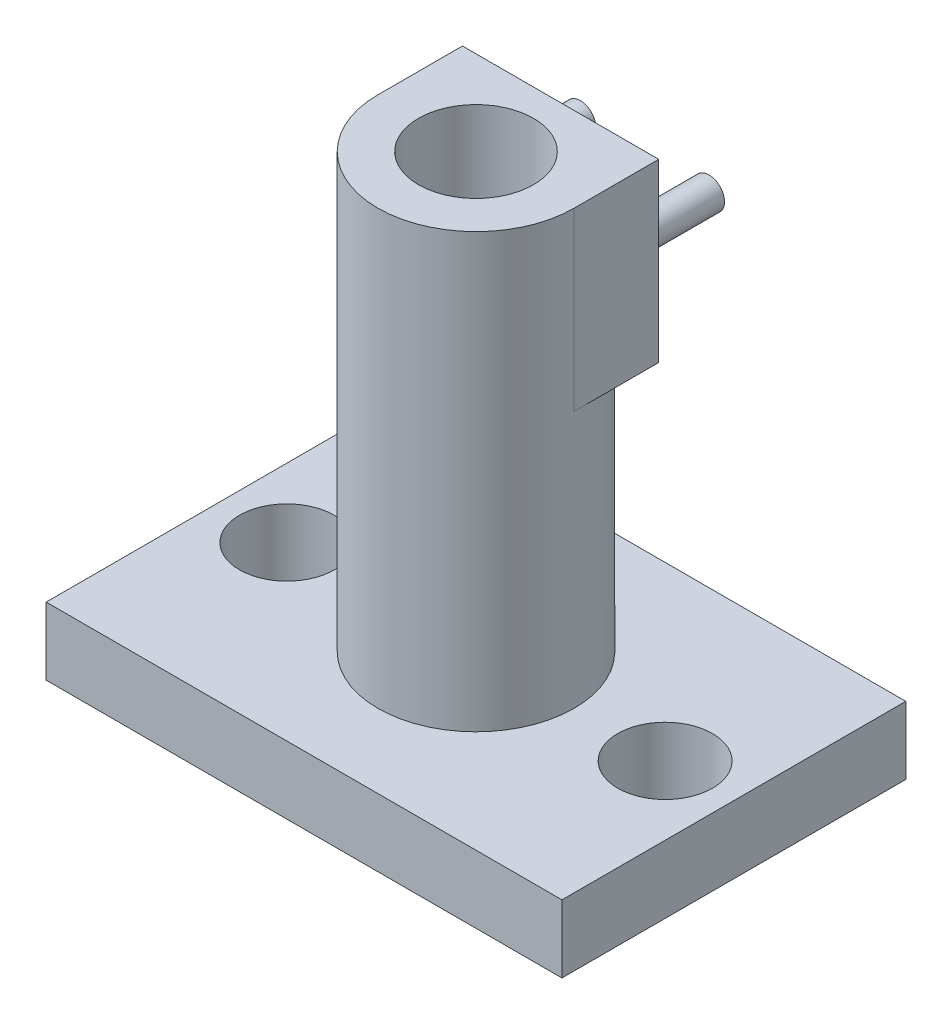
SolidWorks part; units mm, degrees
ref_plane "前视" through (0, 0, 0) normal (0, 0, 1) x (1, 0, 0)
ref_plane "上视" through (0, 0, 0) normal (0, 1, 0) x (1, 0, 0)
ref_plane "右视" through (0, 0, 0) normal (1, 0, 0) x (0, 0, -1)
sketch "Sketch1" plane through (0, 0, 0) normal (0, 1, 0) x (1, 0, 0)
  line L1 (-25.8417, 12.7) -> (12.2583, 12.7)
  line L2 (-25.8417, 12.7) -> (-25.8417, -12.7)
  line L3 (-25.8417, -12.7) -> (12.2583, -12.7)
  line L4 (12.2583, 12.7) -> (12.2583, -12.7)
  dimension "D1" = 25.4
  dimension "D2" = 38.1
extrude "Boss-Extrude1" add sketch "Sketch1" along normal blind 5
ref_point "Point1"
sketch "Sketch3" plane through (0, 5, 0) normal (0, 1, 0) x (1, 0, 0)
  circle A0 centre (-6.7917, 0) radius 7.25
  circle A1 centre (-6.7917, 0) radius 4.25
  dimension "D1" = 8.5
  dimension "D2" = 3
extrude "Boss-Extrude2" add sketch "Sketch3" along normal blind 32
ref_axis "Axis1" through (12.2583, 5, 0) along (-1, 0, 0)
sketch "Sketch4" plane through (0, 5, 0) normal (0, 1, 0) x (1, 0, 0)
  line L0 (12.2583, -12.7) -> (12.2583, 12.7) construction
  line L1 (-25.8417, 12.7) -> (-25.8417, -12.7) construction
  circle A0 centre (7.1783, 0) radius 3.5
  circle A1 centre (-20.7617, 0) radius 3.5
  point P0 (7.1783, 0)
  point P1 (12.2583, 0)
  point P4 (-20.7617, 0)
  dimension "D3" = 7
  dimension "D4" = 7
  dimension "D1" = 5.08
  dimension "D2" = 5.08
extrude "Cut-Extrude1" cut sketch "Sketch4" against normal through all
sketch "Sketch6" plane through (0, 37, 0) normal (0, 1, 0) x (1, 0, 0)
  line L0 (-3.1175, 6.25) -> (-10.466, 6.25)
  line L1 (12.2583, 0) -> (-25.8417, 0) construction
  circle A2 centre (-6.7917, 0) radius 7.25 construction
  arc A3 (-3.1175, 6.25) -> (-10.466, 6.25) centre (-6.7917, 0) ccw
  dimension "D1" = 6.25
extrude "Cut-Extrude2" cut sketch "Sketch6" against normal blind 18
sketch "Sketch8" plane through (0, 37, 0) normal (0, 1, 0) x (1, 0, 0)
  line L0 (-10.466, 6.25) -> (-3.1175, 6.25) construction
  line L1 (-14.0417, 6.25) -> (-10.466, 6.25)
  line L2 (0.4583, 0) -> (0.4583, 6.25)
  line L3 (-14.0417, 0) -> (-14.0417, 6.25)
  line L4 (-3.1175, 6.25) -> (0.4583, 6.25)
  arc A0 (-10.466, 6.25) -> (-3.1175, 6.25) centre (-6.7917, 0) ccw construction
  arc A1 (-10.466, 6.25) -> (-14.0417, 0) centre (-6.7917, 0) ccw
  arc A2 (0.4583, 0) -> (-3.1175, 6.25) centre (-6.7917, 0) ccw
extrude "Boss-Extrude3" add sketch "Sketch8" against normal blind 13
sketch "Sketch9" plane through (0, 0, -6.25) normal (0, 0, -1) x (-1, 0, 0)
  line L0 (6.7917, 37) -> (6.7917, 26.3665) construction
  line L1 (14.0417, 37) -> (-0.4583, 37) construction
  circle A0 centre (2.0417, 30.5) radius 1.15
  circle A1 centre (11.5417, 30.5) radius 1.15
  dimension "D1" = 2.3
  dimension "D2" = 2.3
  dimension "D3" = 9.5
  dimension "D4" = 4.75
  dimension "D5" = 6.5
  dimension "D6" = 6.5
extrude "Boss-Extrude4" add sketch "Sketch9" along normal blind 6.21
